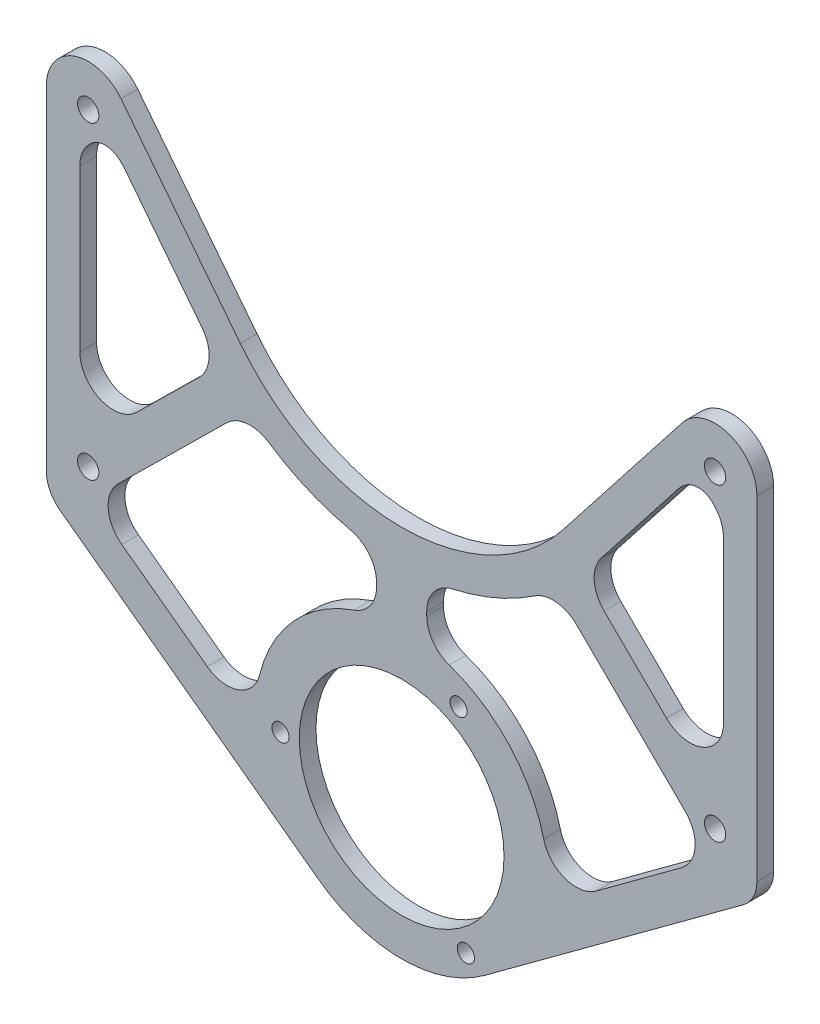
SolidWorks part; units mm, degrees
material "Thornel Mat VMA"
ref_plane "前视基准面" through (0, 0, 0) normal (0, 0, 1) x (1, 0, 0)
ref_plane "上视基准面" through (0, 0, 0) normal (0, 1, 0) x (1, 0, 0)
ref_plane "右视基准面" through (0, 0, 0) normal (1, 0, 0) x (0, 0, -1)
sketch "草图1" plane through (0, 0, 0) normal (0, 0, 1) x (1, 0, 0)
  line L0 (-75, 0) -> (75, 0) construction
  line L1 (-85, -84) -> (85, -84)
  line L2 (-85, -84) -> (-85, 10)
  line L3 (-85, 10) -> (-48.0198, 10)
  line L4 (85, -84) -> (85, 10)
  line L5 (0, 10) -> (0, -84) construction
  line L6 (-85, -37) -> (85, -37) construction
  line L7 (48.0198, 10) -> (85, 10)
  line L8 (-75, -74) -> (75, -74) construction
  line L9 (-75, -74) -> (-75, 0) construction
  line L10 (-75, 0) -> (75, 0) construction
  line L11 (75, -74) -> (75, 0) construction
  line L12 (0, 0) -> (0, -74) construction
  line L13 (-75, -37) -> (75, -37) construction
  arc A0 (-48.0198, 10) -> (48.0198, 10) centre (0, 0) ccw
  circle A1 centre (75, 0) radius 2.55
  circle A2 centre (-75, 0) radius 2.55
  circle A3 centre (-75, -74) radius 2.55
  circle A4 centre (75, -74) radius 2.55
  point P3 (0, -37)
  point P7 (0, -37)
  point P10 (0, 0)
  dimension "D1" = 98.1
  dimension "D6" = 5.1
  dimension "D2" = 170
  dimension "D3" = 10
  dimension "D4" = 150
  dimension "D5" = 74
extrude "凸台-拉伸1" add sketch "草图1" along normal blind 4
sketch "草图2" plane through (0, 0, 4) normal (0, 0, 1) x (1, 0, 0)
  line L0 (0, 0) -> (0, -105) construction
  line L1 (-85, -84) -> (-19.8669, -131.9732)
  line L2 (85, -84) -> (19.8669, -131.9732)
  line L3 (-85, -84) -> (85, -84)
  arc A0 (-19.8669, -131.9732) -> (19.8669, -131.9732) centre (0, -105) ccw
  dimension "D2" = 67
  dimension "D1" = 105
extrude "凸台-拉伸2" add sketch "草图2" against normal up to surface (4 mm away) up to face at (0, -31.175, 0)
fillet "圆角2" radius 10 2 edges at (85, 10, 2) (-85, 10, 2)
sketch "草图5" plane through (0, 0, 4) normal (0, 0, 1) x (1, 0, 0)
  line L0 (0, -105) -> (29, -105) construction
  line L1 (0, -105) -> (15.3677, -129.5934) construction
  line L2 (0, -105) -> (15.3677, -129.5934) construction
  line L3 (0, -105) -> (-28.9823, -106.0121) construction
  circle A0 centre (0, -105) radius 29 construction
  circle A2 centre (15.3677, -129.5934) radius 2.05
  circle A3 centre (-28.9823, -106.0121) radius 2.05
  circle A4 centre (13.6147, -79.3945) radius 2.05
  circle A5 centre (0, -105) radius 24.5
  dimension "D1" = 58
  dimension "D3" = 4.1
  dimension "D2" = 58
  dimension "D5" = 120
  dimension "D6" = 4.5
  dimension "D4" = 3
extrude "切除-拉伸1" cut sketch "草图5" against normal blind 5
sketch "草图6" plane through (0, 0, 4) normal (0, 0, 1) x (1, 0, 0)
  line L0 (-67.1267, 6.1653) -> (-38.6187, -30.2407)
  line L1 (0, 0) -> (0, -105) construction
  line L2 (67.1267, 6.1653) -> (38.6187, -30.2407)
  line L3 (-75, 10) -> (75, 10)
  line L4 (-38.6187, -30.2407) -> (38.6187, -30.2407)
  arc A0 (-67.1267, 6.1653) -> (-75, 10) centre (-75, 0) ccw
  arc A1 (75, 10) -> (67.1267, 6.1653) centre (75, 0) ccw
  arc A3 (-48.0198, 10) -> (48.0198, 10) centre (0, 0) ccw construction
extrude "切除-拉伸2" cut sketch "草图6" against normal blind 5
sketch "草图7" plane through (0, 0, 4) normal (0, 0, 1) x (1, 0, 0)
  line L0 (0, -49.05) -> (0, -105) construction
  line L1 (-6, -56.7336) -> (-6, -70.5181)
  line L2 (6, -56.7336) -> (6, -70.5181)
  line L3 (-75, -74) -> (0, 0) construction
  line L4 (0, 0) -> (75, -74) construction
  line L5 (-74.5146, -80.5452) -> (-36.9423, -43.4738)
  line L6 (36.9423, -43.4738) -> (74.5146, -80.5452)
  line L7 (-77, -70.3541) -> (-43.3596, -37.1622)
  line L8 (6, -49.05) -> (6, -81) construction
  line L9 (-77, -5.1448) -> (-77, -70.3541)
  line L11 (-68.8572, -4.6007) -> (-43.3596, -37.1622)
  line L12 (-67.1267, 6.1653) -> (-38.6187, -30.2407) construction
  line L13 (-85, 0) -> (-85, -84) construction
  line L14 (-77, -5.1448) -> (-68.8572, -4.6007)
  line L15 (-6.1089, -0.4082) -> (0, 0)
  line L16 (-77.8094, -71.1527) -> (0, 5.6193) construction
  line L17 (-74.5146, -80.5452) -> (-34.6548, -109.9036)
  line L18 (-85, -84) -> (-19.8669, -131.9732) construction
  line L19 (-71.4883, -77.5592) -> (0, -7.0241) construction
  line L20 (-6.1089, -0.4082) -> (0, 5.6193)
  line L21 (74.5146, -80.5452) -> (34.6548, -109.9036)
  line L22 (0, -7.0241) -> (71.4883, -77.5592) construction
  line L23 (0, 5.6193) -> (77.8094, -71.1527) construction
  line L24 (-6, -49.05) -> (-6, -81) construction
  line L25 (77, -5.1448) -> (77, -70.3541)
  line L26 (77, -5.1448) -> (68.8572, -4.6007)
  line L27 (68.8572, -4.6007) -> (43.3596, -37.1622)
  line L28 (77, -70.3541) -> (43.3596, -37.1622)
  line L29 (0, -49.05) -> (0, -81) construction
  arc A0 (-38.6187, -30.2407) -> (38.6187, -30.2407) centre (0, 0) ccw construction
  arc A1 (-6, -70.5181) -> (-34.6548, -109.9036) centre (0, -105) ccw
  circle A2 centre (-75, 0) radius 2.55 construction
  arc A4 (-36.9423, -43.4738) -> (-6, -56.7336) centre (0, 0) ccw
  arc A5 (6, -56.7336) -> (36.9423, -43.4738) centre (0, 0) ccw
  arc A6 (34.6548, -109.9036) -> (6, -70.5181) centre (0, -105) ccw
  dimension "D3" = 70
  dimension "D8" = 5
  dimension "D10" = 8
  dimension "D6" = 8
  dimension "D7" = 8
  dimension "D9" = 9
  dimension "D1" = 6
  dimension "D2" = 6
  dimension "D4" = 5
  dimension "D5" = 4
extrude "切除-拉伸3" cut sketch "草图7" against normal blind 25 contours L14 L9 L7 L11 | A4 L5 L17 A1 L1 | A6 L21 L6 A5 L2 | L28 L25 L26 L27 region at (-39.3194, -73.4543, 4) region at (39.3194, -73.4543, 4) region at (-65.4803, -35.0805, 4) region at (65.4803, -35.0805, 4)
fillet "圆角3" radius 8 20 edges at (-6, -56.7336, 2) (-6, -70.5181, 2) (-34.6548, -109.9036, 2) (-74.5146, -80.5452, 2) (-36.9423, -43.4738, 2) (43.3596, -37.1622, 2) (68.8572, -4.6007, 2) (77, -5.1448, 2) (77, -70.3541, 2) (-85, -84, 2) (85, -84, 2) (-68.8572, -4.6007, 2) (-43.3596, -37.1622, 2) (-77, -70.3541, 2) (-77, -5.1448, 2) (6, -56.7336, 2) (36.9423, -43.4738, 2) (74.5146, -80.5452, 2) (6, -70.5181, 2) (34.6548, -109.9036, 2)
fillet "圆角4" radius 5 2 edges at (71.2933, -4.9638, 2) (-71.2933, -4.9638, 2)
